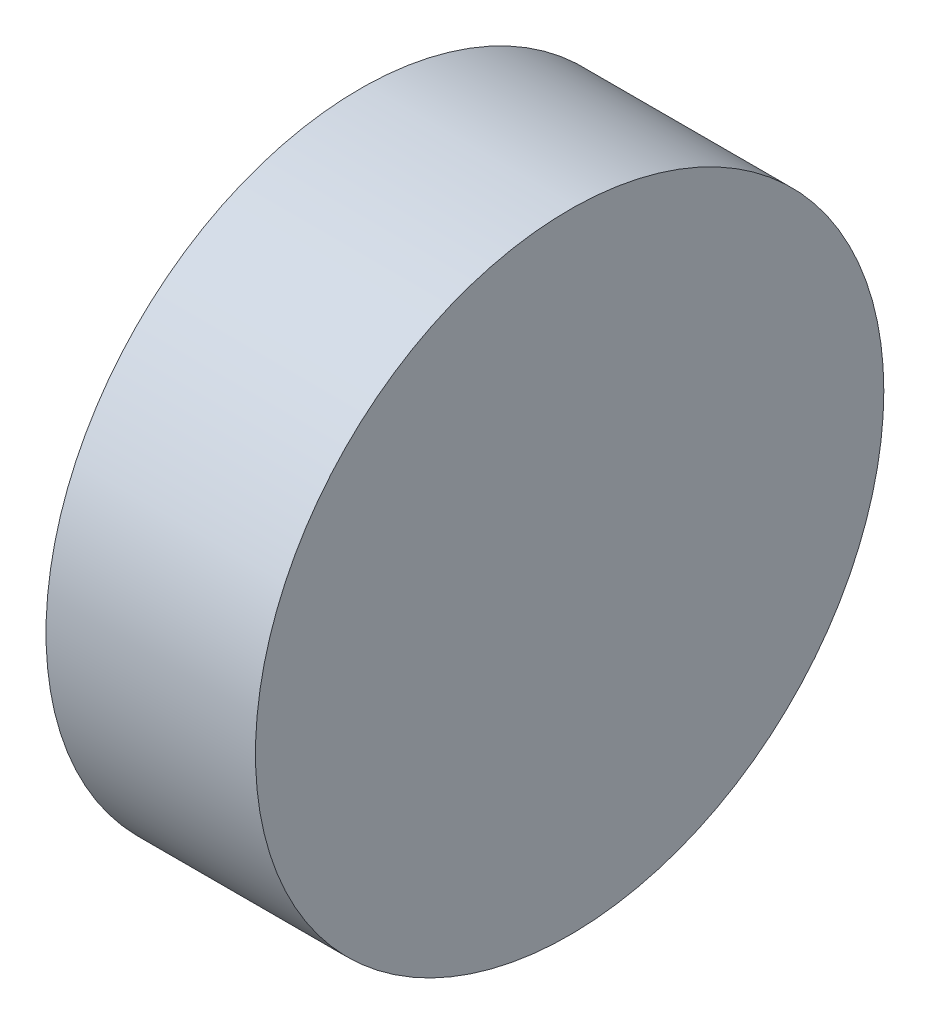
SolidWorks part; units mm, degrees
ref_plane "Front Plane" through (0, 0, 0) normal (0, 0, 1) x (1, 0, 0)
ref_plane "Top Plane" through (0, 0, 0) normal (0, 1, 0) x (1, 0, 0)
ref_plane "Right Plane" through (0, 0, 0) normal (1, 0, 0) x (0, 0, -1)
sketch "Sketch1" plane through (0, 0, 0) normal (1, 0, 0) x (0, 0, -1)
  circle A0 centre (0, 0) radius 3
  dimension "D1" = 6
extrude "Boss-Extrude1" add sketch "Sketch1" along normal blind 1 and the other way blind 1
